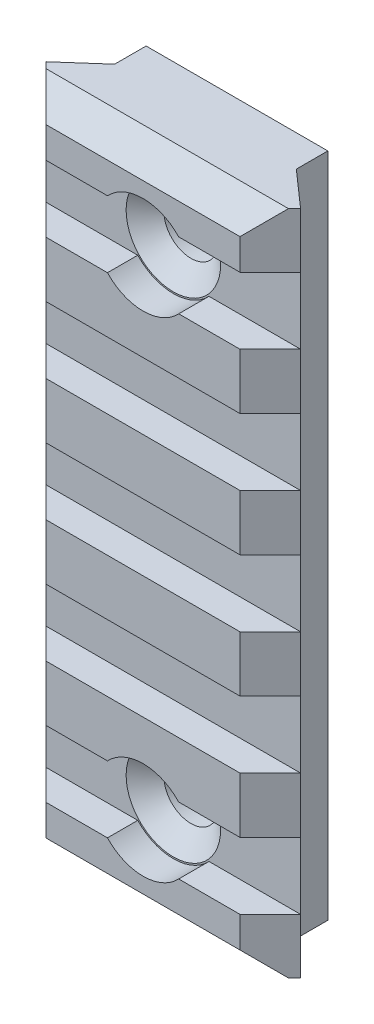
SolidWorks part; units mm, degrees
ref_plane "정면" through (0, 0, 0) normal (0, 0, 1) x (1, 0, 0)
ref_plane "윗면" through (0, 0, 0) normal (0, 1, 0) x (1, 0, 0)
ref_plane "우측면" through (0, 0, 0) normal (1, 0, 0) x (0, 0, -1)
sketch "스케치1" plane through (0, 0, 0) normal (0, 1, 0) x (1, 0, 0)
  line L1 (-7.5, 0) -> (7.5, 0)
  line L2 (7.5, 0) -> (7.5, -2.6)
  line L3 (7.5, -2.6) -> (10.5, -5.25)
  line L4 (10.5, -5.25) -> (8, -7.75)
  line L5 (8, -7.75) -> (-8, -7.75)
  line L6 (0, 0) -> (0, -7.75) construction
  line L7 (-7.5, 0) -> (-7.5, -2.6)
  line L8 (-7.5, -2.6) -> (-10.5, -5.25)
  line L9 (-10.5, -5.25) -> (-8, -7.75)
  dimension "D1" = 15
  dimension "D2" = 21
  dimension "D3" = 7.75
  dimension "D4" = 2.6
  dimension "D5" = 5.25
  dimension "D6" = 16
extrude "보스-돌출1" add sketch "스케치1" along normal blind 55
sketch "스케치2" plane through (0, 0, 0) normal (1, 0, 0) x (0, 0, -1)
  line L0 (-7.75, 55) -> (-7.75, 0) construction
  line L1 (-7.75, 4.55) -> (-5.25, 4.55)
  line L2 (-7.75, 4.55) -> (-7.75, 10.05)
  line L3 (-7.75, 10.05) -> (-5.25, 10.05)
  line L4 (-5.25, 4.55) -> (-5.25, 10.05)
  line L5 (-5.25, 55) -> (-5.25, 0) construction
  line L6 (-7.75, 20.15) -> (-5.25, 20.15)
  line L7 (-7.75, 14.65) -> (-7.75, 20.15)
  line L8 (-7.75, 14.65) -> (-5.25, 14.65)
  line L9 (-5.25, 14.65) -> (-5.25, 20.15)
  line L10 (-7.75, 30.25) -> (-5.25, 30.25)
  line L11 (-7.75, 24.75) -> (-7.75, 30.25)
  line L12 (-7.75, 24.75) -> (-5.25, 24.75)
  line L13 (-5.25, 24.75) -> (-5.25, 30.25)
  line L14 (-7.75, 40.35) -> (-5.25, 40.35)
  line L15 (-7.75, 34.85) -> (-7.75, 40.35)
  line L16 (-7.75, 34.85) -> (-5.25, 34.85)
  line L17 (-5.25, 34.85) -> (-5.25, 40.35)
  line L18 (-7.75, 50.45) -> (-5.25, 50.45)
  line L19 (-7.75, 44.95) -> (-7.75, 50.45)
  line L20 (-7.75, 44.95) -> (-5.25, 44.95)
  line L21 (-5.25, 44.95) -> (-5.25, 50.45)
  line L22 (-2.6, 55) -> (0, 55) construction
  dimension "D1" = 5.5
  dimension "D3" = 4.55
  dimension "D4" = 4.6
  dimension "D5" = 4.55
  dimension "D2" = 5
extrude "컷-돌출1" cut sketch "스케치2" against normal through all both and the other way through all
chamfer "모따기1" distance 2 angle 45 2 edges at (0, 55, 7.75) (0, 0, 7.75)
sketch "스케치3" plane through (0, 0, 0) normal (0, 0, 1) x (1, 0, 0)
  line L0 (-10.5, 7.3) -> (10.5, 7.3) construction
  line L1 (-10.5, 4.55) -> (-10.5, 10.05) construction
  line L2 (10.5, 4.55) -> (10.5, 10.05) construction
  line L3 (-10.5, 47.7) -> (10.5, 47.7) construction
  line L4 (-10.5, 44.95) -> (-10.5, 50.45) construction
  line L5 (10.5, 44.95) -> (10.5, 50.45) construction
  circle A0 centre (0, 47.7) radius 1.9
  circle A1 centre (0, 7.3) radius 1.9
  dimension "D1" = 3.8
  dimension "D2" = 3.8
extrude "컷-돌출2" cut sketch "스케치3" along normal through all
sketch "스케치4" plane through (0, 0, 7.75) normal (0, 0, 1) x (1, 0, 0)
  circle A0 centre (0, 7.3) radius 4.025
  circle A1 centre (0, 47.7) radius 4.025
  dimension "D1" = 8.05
  dimension "D2" = 8.05
extrude "컷-돌출3" cut sketch "스케치4" against normal up to surface (2.5 mm away) up to face at (-1.9, 7.3, 5.25)
chamfer "모따기2" distance 2 angle 41 2 edges at (-1.9, 47.7, 5.25) (-1.9, 7.3, 5.25) first distance on face at (0, 47.7, 5.25) first distance on face at (0, 7.3, 5.25)
sketch "스케치5" plane through (0, 0, 0) normal (0, 0, 1) x (1, 0, 0)
  line L0 (0, 50.8) -> (0, 47.7) construction
  line L1 (2.95, 50.8) -> (2.95, 47.7)
  line L2 (-2.95, 50.8) -> (-2.95, 47.7)
  line L3 (0, 7.3) -> (0, 10.4) construction
  line L4 (-2.95, 7.3) -> (-2.95, 10.4)
  line L5 (2.95, 7.3) -> (2.95, 10.4)
  line L6 (0, 53.75) -> (0, 44.75) construction
  line L7 (0, 13.35) -> (0, 4.35) construction
  arc A0 (2.95, 50.8) -> (-2.95, 50.8) centre (0, 50.8) ccw
  arc A1 (-2.95, 47.7) -> (2.95, 47.7) centre (0, 47.7) ccw
  arc A2 (-2.95, 7.3) -> (2.95, 7.3) centre (0, 7.3) ccw
  arc A3 (2.95, 10.4) -> (-2.95, 10.4) centre (0, 10.4) ccw
  point P4 (0, 49.25)
  point P9 (0, 8.85)
  dimension "D1" = 5.9
  dimension "D2" = 5.9
  dimension "D3" = 9
  dimension "D4" = 9
extrude "컷-돌출4" cut sketch "스케치5" along normal blind 3.8
sketch "스케치6" plane through (0, 0, 0) normal (0, 0, 1) x (1, 0, 0)
  line L0 (0, 0) -> (0, 55) construction
  line L1 (7.5, 55) -> (-7.5, 55) construction
  line L2 (2.8696, 11.084) -> (-2.8696, 11.084) construction
  line L3 (-2.8696, 11.084) -> (-2.8696, 15.17)
  line L4 (-3.316, 15.7559) -> (-4.2384, 15.8942)
  line L5 (3.316, 15.7559) -> (4.2384, 15.8942)
  line L6 (2.8696, 11.084) -> (2.8696, 15.17)
  arc A0 (2.8696, 11.084) -> (-2.8696, 11.084) centre (0, 10.4) ccw
  arc A3 (-2.8696, 15.17) -> (-3.316, 15.7559) centre (-3.3944, 15.2332) ccw
  arc A4 (-4.2384, 15.8942) -> (-4.675, 16.17) centre (-4.1435, 16.5279) cw
  arc A5 (-4.675, 16.17) -> (0, 20.984) centre (0, 16.307) cw
  arc A6 (4.2384, 15.8942) -> (4.675, 16.17) centre (4.1435, 16.5279) ccw
  arc A7 (2.8696, 15.17) -> (3.316, 15.7559) centre (3.3944, 15.2332) cw
  arc A8 (4.675, 16.17) -> (0, 20.984) centre (0, 16.307) ccw
  point P9 (0, 0)
  dimension "D2" = 9.35
  dimension "D3" = 9.9
  dimension "D4" = 1
extrude "보스-돌출2" add sketch "스케치6" against normal blind 1
fillet "필렛1" radius 0.1 2 edges
